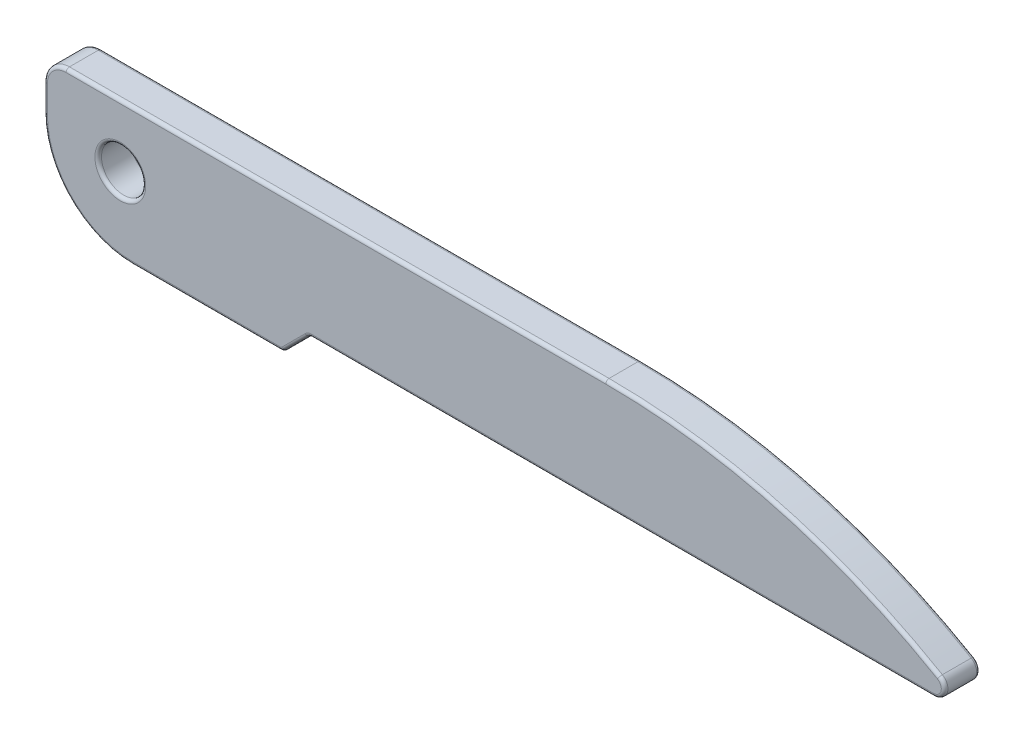
SolidWorks part; units mm, degrees
material "1060 Alloy"
ref_plane "Front Plane" through (0, 0, 0) normal (0, 0, 1) x (1, 0, 0)
ref_plane "Top Plane" through (0, 0, 0) normal (0, 1, 0) x (1, 0, 0)
ref_plane "Right Plane" through (0, 0, 0) normal (1, 0, 0) x (0, 0, -1)
sketch "Sketch1" plane through (0, 0, 0) normal (0, 0, 1) x (1, 0, 0)
  line L0 (0, 0) -> (0, 6.2)
  line L1 (0, 6.2) -> (25.4169, 6.2)
  line L2 (42, 1.2) -> (12, 1.2)
  line L3 (12, 1.2) -> (10.8, 0)
  line L4 (10.8, 0) -> (0, 0)
  arc A0 (25.4169, 6.2) -> (42, 1.2) centre (25.4169, -23.8) cw
  dimension "D2" = 30
  dimension "D1" = 6.2
  dimension "D3" = 5
  dimension "D4" = 45
  dimension "D5" = 42
  dimension "D6" = 30
extrude "Boss-Extrude1" add sketch "Sketch1" along normal blind 1.6
fillet "Fillet1" radius 0.5 1 edges at (42, 1.2, 0.8)
fillet "Fillet2" radius 0.25 2 edges at (10.8, 0, 0.8) (12, 1.2, 0.8)
fillet "Fillet3" radius 0.15 18 edges at (10.7921, 0.019, 0) (11.4, 0.6, 0) (12.0079, 1.181, 0) (26.1764, 1.2, 0) (40.732, 1.5698, 0) (33.2282, 5.1652, 0) (12.7084, 6.2, 0) (0, 3.1, 0) (5.3482, 0, 0) (12.7084, 6.2, 1.6) (33.2282, 5.1652, 1.6) (40.732, 1.5698, 1.6) (26.1764, 1.2, 1.6) (12.0079, 1.181, 1.6) (11.4, 0.6, 1.6) (10.7921, 0.019, 1.6) (5.3482, 0, 1.6) (0, 3.1, 1.6)
sketch "Sketch2" plane through (0, 0, 0) normal (0, 0, -1) x (-1, 0, 0)
  line L0 (-16.4169, 5.55) -> (-28.4169, 5.55)
  line L1 (-0.15, 6.05) -> (-25.4169, 6.05) construction
  arc A0 (-28.4169, 5.55) -> (-16.4169, 5.55) centre (-22.4169, 19.2977) ccw
  dimension "D4" = 15
  dimension "D1" = 12
  dimension "D2" = 3
  dimension "D3" = 0.5
extrude "Cut-Extrude1" cut sketch "Sketch2" against normal blind 0.3 contours A0 L0
fillet "Fillet4" radius 4 1 edges at (22.4169, 4.2977, 0.3)
sketch "Sketch3" plane through (0, 0, 0) normal (0, 0, -1) x (-1, 0, 0)
  line L1 (0, 6.2) -> (0, 0) construction
  line L2 (0, 6.2) -> (-25.4169, 6.2) construction
  circle A0 centre (-3.45, 3.4) radius 1
  dimension "D1" = 2
  dimension "D2" = 2.8
  dimension "D3" = 3.45
extrude "Cut-Extrude2" cut sketch "Sketch3" against normal through all
fillet "Fillet5" radius 4 3 edges at (0.0439, 0.0439, 0.0439) (0.0439, 0.0439, 1.5561) (0, 0, 0.8)
fillet "Fillet6" radius 1 3 edges at (0.0439, 6.1561, 0.0439) (0.0439, 6.1561, 1.5561) (0, 6.2, 0.8)
fillet "Fillet7" radius 0.15 2 edges at (2.45, 3.4, 0) (2.45, 3.4, 1.6)
